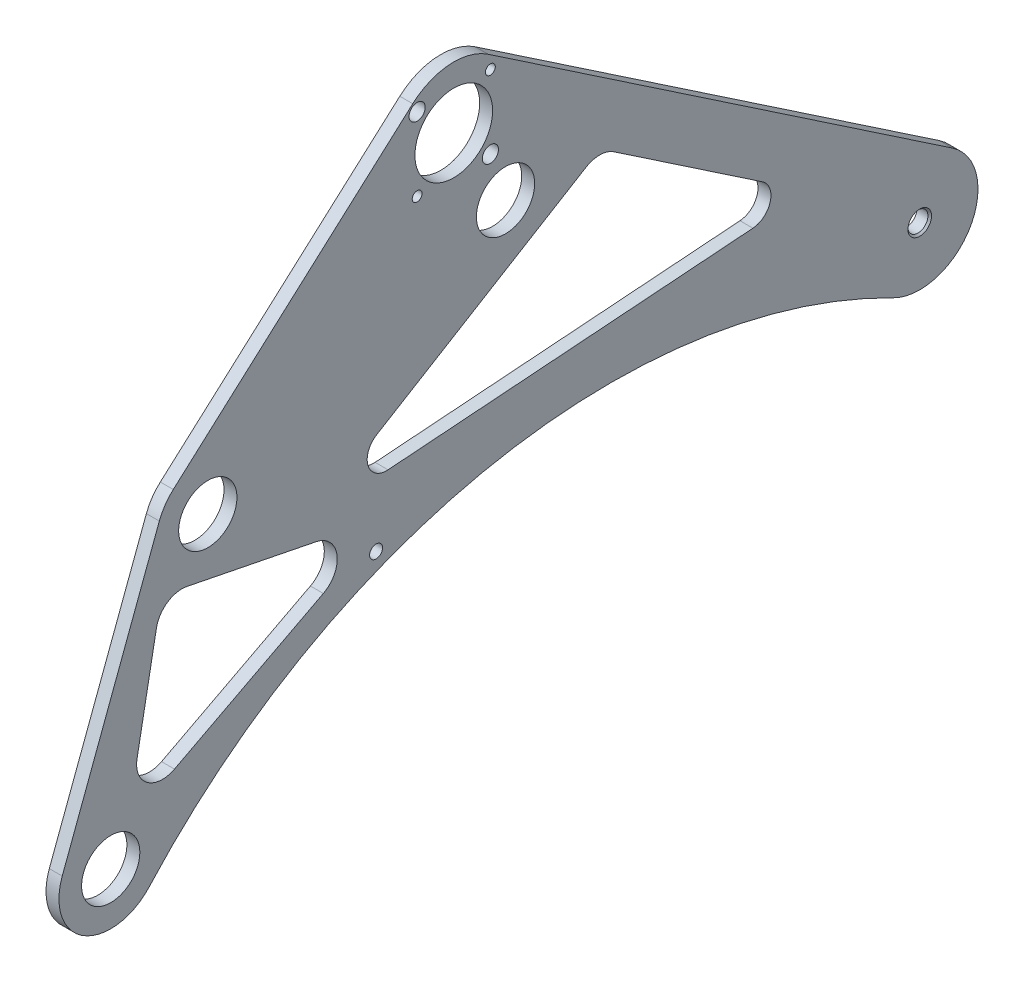
SolidWorks part; units mm, degrees
material "Acrylic (Medium-high impact)"
ref_plane "Front Plane" through (0, 0, 0) normal (0, 0, 1) x (1, 0, 0)
ref_plane "Top Plane" through (0, 0, 0) normal (0, 1, 0) x (1, 0, 0)
ref_plane "Right Plane" through (0, 0, 0) normal (1, 0, 0) x (0, 0, -1)
sketch "Sketch1" plane through (0, 0, 0) normal (1, 0, 0) x (0, 0, -1)
  line L0 (-548.7618, -304.8) -> (152.435, -304.8)
  line L1 (-192.8252, -101.6) -> (-152.4, -101.6)
  line L2 (-234.95, -143.7248) -> (-234.95, -186.4752)
  line L3 (-192.8252, -228.6) -> (-152.4, -228.6)
  line L4 (-152.4, -101.6) -> (-152.4, -228.6)
  line L10 (-225.1934, 154.4964) -> (-199.7934, 113.2214)
  line L11 (-200.4191, 108.2498) -> (-394.0941, -79.0752)
  line L12 (-400.6203, -74.7955) -> (-352.9953, 52.2045)
  line L13 (-350.2484, 54.6734) -> (-296.1816, 68.6089)
  line L14 (-293.9553, 70.1155) -> (-231.8247, 154.7668)
  circle A1 centre (0, 0) radius 6.35
  circle A6 centre (-396.875, -76.2) radius 9.525
  circle A7 centre (-349.25, 50.8) radius 9.525
  circle A8 centre (-203.2, 111.125) radius 9.525
  arc A9 (-234.95, -186.4752) -> (-192.8252, -228.6) centre (-192.8252, -186.4752) ccw
  arc A10 (-192.8252, -101.6) -> (-234.95, -143.7248) centre (-192.8252, -143.7248) ccw
  circle A11 centre (-230.9942, 0) radius 120.65
  circle A12 centre (-228.6, 152.4) radius 29.845
  arc A23 (-231.8247, 154.7668) -> (-225.1934, 154.4964) centre (-228.6, 152.4) cw
  arc A24 (-199.7934, 113.2214) -> (-200.4191, 108.2498) centre (-203.2, 111.125) cw
  arc A25 (-394.0941, -79.0752) -> (-400.6203, -74.7955) centre (-396.875, -76.2) cw
  arc A26 (-352.9953, 52.2045) -> (-350.2484, 54.6734) centre (-349.25, 50.8) cw
  arc A27 (-296.1816, 68.6089) -> (-293.9553, 70.1155) centre (-297.18, 72.4823) ccw
  circle B0 centre (-349.25, 50.8) radius 4
  line B1 (-396.875, -76.2) -> (-382.9261, -60.8997)
  circle B2 centre (-396.875, -76.2) radius 4
  circle B3 centre (-203.2, 111.125) radius 4
  line B4 (-228.6, 152.4) -> (-225.2662, 168.6097)
  circle B5 centre (-228.6, 152.4) radius 4
  circle B6 centre (-297.18, 72.4823) radius 4
  dimension "D1" = 12.7
  dimension "D2" = 19.05
  dimension "D3" = 42.1248
  dimension "D4" = 127
  dimension "D7" = 203.2
  dimension "D6" = 241.3
  dimension "D16" = 59.69
  dimension "D5" = 82.55
  dimension "D8" = 304.8
  dimension "D9" = 152.4
  dimension "D10" = 396.875
  dimension "D11" = 76.2
  dimension "D12" = 349.25
  dimension "D13" = 50.8
  dimension "D14" = 203.2
  dimension "D15" = 111.125
  dimension "D17" = 228.6
  dimension "D18" = 152.4
  dimension "D23" = 297.18
sketch_block_instance "Block1-1"
sketch_block "Block1"
sketch_block_instance "Block2-1"
sketch_block "Block2"
sketch_block_instance "Block3-1"
sketch_block "Block3"
sketch_block_instance "Block4-1"
sketch_block "Block4" parameters "D1"=8
sketch_block_instance "Block5-1"
sketch_block "Block5"
other "Belt1"
sketch "Sketch2" plane through (0, 0, 0) normal (1, 0, 0) x (0, 0, -1)
  line L1 (-420.6578, -67.2815) -> (-373.0328, 59.7185)
  line L3 (-366.1902, 69.7259) -> (-248.7165, 174.8745)
  line L5 (-211.7241, 177.3996) -> (15.9877, 23.6839)
  line L6 (-1001.8623, -101.6) -> (216.545, -101.6) construction
  line L7 (-1029.8132, 182.5625) -> (188.5941, 182.5625) construction
  arc A0 (-366.1902, 69.7259) -> (-373.0328, 59.7185) centre (-349.25, 50.8) ccw
  arc A2 (-420.6578, -67.2815) -> (-377.9906, -93.1865) centre (-396.875, -76.2) ccw
  arc A4 (-211.7241, 177.3996) -> (-248.7165, 174.8745) centre (-228.6, 152.4) ccw
  arc A5 (-12.9753, -25.4592) -> (15.9877, 23.6839) centre (0, 0) ccw
  arc A8 (-377.9906, -93.1865) -> (-12.9753, -25.4592) centre (-151.3783, -297.0244) cw
  circle A12 centre (-396.875, -76.2) radius 9.525 construction
  circle A13 centre (-349.25, 50.8) radius 9.525 construction
  dimension "D1" = 25.4
  dimension "D2" = 57.15
  dimension "D3" = 60.325
  dimension "D4" = 304.8
  dimension "D6" = 284.1625
extrude "Boss-Extrude1" add sketch "Sketch2" along normal blind 6.35
sketch "Sketch3" plane through (6.35, 0, 0) normal (1, 0, 0) x (0, 0, -1)
  line L0 (-210.6395, 170.3605) -> (-246.5605, 134.4395) construction
  line L1 (-228.6, 152.4) -> (-228.6, 205.0182) construction
  line L2 (-246.5605, 170.3605) -> (-210.6395, 134.4395) construction
  circle A0 centre (-203.2, 111.125) radius 14.2875
  circle A1 centre (-349.25, 50.8) radius 14.2875
  circle A2 centre (-396.875, -76.2) radius 14.2875
  circle A3 centre (-228.6, 152.4) radius 19.05
  circle A5 centre (-246.5605, 134.4395) radius 2.413
  circle A7 centre (-210.6395, 134.4395) radius 3.9687
  circle A8 centre (-210.6395, 170.3605) radius 2.413
  circle A9 centre (-246.5605, 170.3605) radius 3.9687
  point P18 (-228.6, 152.4)
  point P28 (-228.6, 152.4)
  dimension "D1" = 38.1
  dimension "D2" = 28.575
  dimension "D3" = 4.826
  dimension "D4" = 50.8
  dimension "D5" = 45
  dimension "D6" = 7.9375
  dimension "D7" = 50.8
extrude "Cut-Extrude1" cut sketch "Sketch3" against normal up to next
hole_wizard "3/8 Clearance Hole2" positions "Sketch7" profile "Sketch8" hole size "3/8" standard "ANSI Inch" end condition through all
sketch "Sketch7" plane through (6.35, 0, 0) normal (1, 0, 0) x (0, 0, -1)
  point P0 (0, 0)
sketch "Sketch8" plane through (6.35, 0, 0) normal (0, 1, 0) x (0, 0, -1)
  line L0 (0, 0) -> (0, 6.35)
  line L1 (0, 6.35) -> (4.9022, 6.35)
  line L2 (4.9022, 6.35) -> (4.9022, 0.8915)
  line L3 (4.9022, 0.8915) -> (5.7937, 0)
  line L5 (5.7937, 0) -> (0, 0)
  line L6 (-4.9022, 0.8915) -> (-5.7937, 0) construction
  line L11 (0, -6.35) -> (0, 107.95) construction
  dimension "Thru Hole Dia." = 9.8044
  dimension "Thru Hole Depth" = 6.35
  dimension "Near C'Sink Dia." = 11.5875
  dimension "Near C'Sink Angle" = 90
sketch "Sketch9" plane through (6.35, 0, 0) normal (1, 0, 0) x (0, 0, -1)
  line L0 (-495.9857, -101.6) -> (27.4607, -101.6) construction
  line L1 (100.4878, 182.5625) -> (-422.9585, 182.5625) construction
  arc A0 (-211.7241, 177.3996) -> (-248.7165, 174.8745) centre (-228.6, 152.4) ccw construction
  arc A1 (-420.6578, -67.2815) -> (-377.9906, -93.1865) centre (-396.875, -76.2) ccw construction
  dimension "D1" = 284.1625
hole_wizard "1/4 (0.2500) Dowel Hole2" positions "Sketch12" profile "Sketch13" hole size "1/4" standard "ANSI Inch" end condition through all
sketch "Sketch12" plane through (6.35, 0, 0) normal (1, 0, 0) x (0, 0, -1)
  point P0 (-266.7, -6.35)
  dimension "D1" = 266.7
sketch "Sketch13" plane through (6.35, -6.35, 266.7) normal (0, 1, 0) x (0, 0, -1)
  line L0 (0, 0) -> (0, 6.35)
  line L1 (0, 6.35) -> (3.175, 6.35)
  line L2 (3.175, 6.35) -> (3.175, 0)
  line L5 (3.175, 0) -> (0, 0)
  line L11 (0, -6.35) -> (0, 107.95) construction
  dimension "Thru Hole Dia." = 6.35
  dimension "Thru Hole Depth" = 6.35
sketch "Sketch14" plane through (6.35, 0, 0) normal (1, 0, 0) x (0, 0, -1)
  line L0 (-365.6004, -49.3596) -> (-292.5754, -11.2596)
  line L1 (-295.9593, 12.4534) -> (-359.4593, 25.1534)
  line L2 (-374.4325, 15.0405) -> (-383.9575, -35.7595)
  line L3 (-77.2075, 55.9493) -> (-149.9685, 105.0662)
  line L4 (-163.6599, 105.3991) -> (-266.4749, 43.0436)
  line L6 (-260.8375, 25.4) -> (-81.8386, 38.5553)
  line L9 (15.9877, 23.6839) -> (-211.7241, 177.3996) construction
  arc A0 (-383.9575, -35.7595) -> (-365.6004, -49.3596) centre (-371.475, -38.1) ccw
  arc A1 (-292.5754, -11.2596) -> (-295.9593, 12.4534) centre (-298.45, 0) ccw
  arc A2 (-359.4593, 25.1534) -> (-374.4325, 15.0405) centre (-361.95, 12.7) ccw
  circle A3 centre (-396.875, -76.2) radius 14.2875 construction
  circle A4 centre (-349.25, 50.8) radius 14.2875 construction
  circle A5 centre (-266.7, -6.35) radius 3.175 construction
  arc A9 (-149.9685, 105.0662) -> (-163.6599, 105.3991) centre (-157.0742, 94.5401) ccw
  arc A13 (-260.8375, 25.4) -> (-266.4749, 43.0436) centre (-261.5356, 34.8994) cw
  circle A15 centre (-203.2, 111.125) radius 14.2875 construction
  arc A21 (-81.8386, 38.5553) -> (-77.2075, 55.9493) centre (-82.5367, 48.0546) ccw
  point P21 (0, 0)
  point P28 (0, 0)
  point P31 (-259.0161, 21.9028)
  point P35 (-259.9587, 29.0065)
  point P36 (-260.0482, 34.8992)
  point P44 (-288.2635, 17.3613)
  dimension "D1" = 38.1
  dimension "D2" = 25.4
  dimension "D3" = 25.4
  dimension "D4" = 38.1
  dimension "D5" = 12.7
  dimension "D6" = 31.75
  dimension "D7" = 6.35
  dimension "D8" = 25.4
  dimension "D9" = 25.4
  dimension "D12" = 9.525
  dimension "D13" = 25.4
  dimension "D14" = 12.7
  dimension "D15" = 44.45
  dimension "D16" = 50.8
  dimension "D11" = 9.525
  dimension "D10" = 25.4
extrude "Cut-Extrude2" cut sketch "Sketch14" against normal through all
